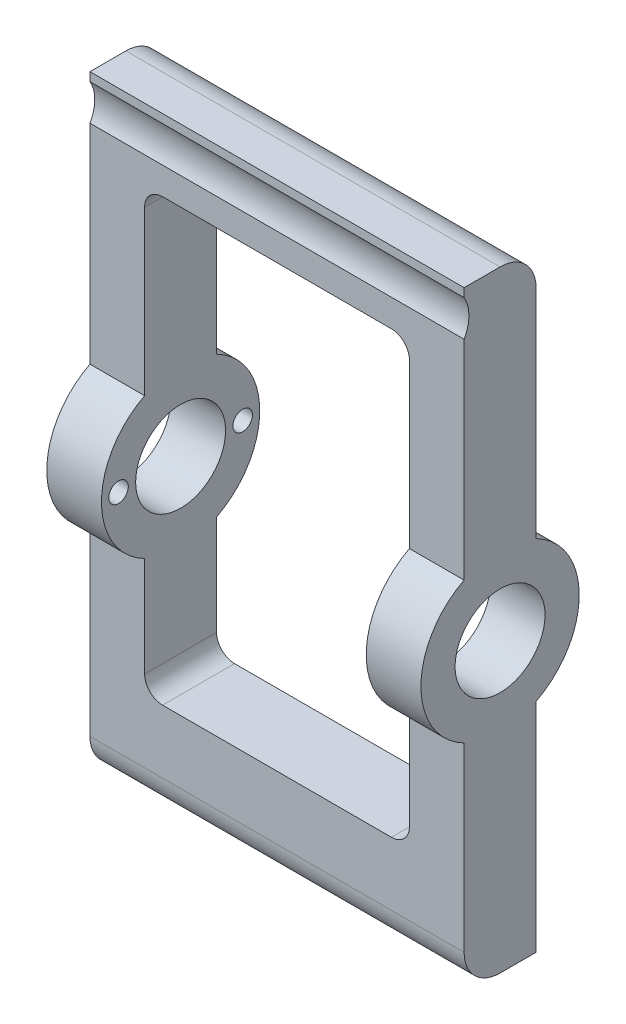
SolidWorks part; units mm, degrees
material "AISI 4130 Steel, annealed at 865C"
ref_plane "Front Plane" through (0, 0, 0) normal (1, 0, 0) x (0, 1, 0)
ref_plane "Top Plane" through (0, 0, 0) normal (0, 0, 1) x (0, 1, 0)
ref_plane "Right Plane" through (0, 0, 0) normal (0, 1, 0) x (-1, 0, 0)
sketch "Sketch1" plane through (0, 0, 0) normal (1, 0, 0) x (0, 1, 0)
  line L0 (12.4434, 6.35) -> (49.276, 6.35)
  line L5 (57.15, 0) -> (-57.15, 0) construction
  line L6 (12.4434, -6.35) -> (57.15, -6.35)
  line L7 (57.15, -6.35) -> (57.15, 6.35)
  line L8 (57.15, 6.35) -> (55.626, 6.35)
  line L9 (12.4434, -6.35) -> (12.4434, 6.35) construction
  line L10 (0, 13.97) -> (0, -13.97) construction
  line L11 (-12.4434, 6.35) -> (-50.8, 6.35)
  line L12 (-12.4434, 6.35) -> (-12.4434, -6.35)
  line L13 (-12.4434, -6.35) -> (-50.8, -6.35)
  line L14 (-50.8, 6.35) -> (-50.8, -6.35)
  line L15 (0, -10.9601) -> (0, 10.9601)
  line L16 (-7.5565, 2.4297) -> (-7.5565, -2.4297)
  line L17 (52.451, 11.8493) -> (49.276, 6.35) construction
  circle A0 centre (0, 0) radius 7.9375
  circle A1 centre (0, 0) radius 13.97
  arc A2 (49.276, 6.35) -> (55.626, 6.35) centre (52.451, 11.8493) ccw
  circle A3 centre (52.451, 11.8493) radius 6.35 construction
  point P9 (0, 0)
  point P17 (12.4434, 0)
  point P28 (0, 0)
  dimension "D1" = 15.875
  dimension "D3" = 27.94
  dimension "D7" = 6.35
  dimension "D2" = 12.7
  dimension "D4" = 57.15
  dimension "D5" = 50.8
  dimension "D6" = 1.524
  dimension "D8" = 6.35
  dimension "D9" = 21.9202
  dimension "D10" = 7.5565
extrude "Boss-Extrude1" add sketch "Sketch1" along normal blind 66.04 contours A1 L11 L14 L13 | L12 A1 | A1 L12 A0 | A2 L0 A1 L6 L7 L8 region at (0, 35.1954, -0.0398) region at (0, 13.2092, 3.1756) region at (0, -32.1337, 0) region at (0, -13.057, 0)
sketch "Sketch2" plane through (0, 0, 0) normal (0, 0, 1) x (0, 1, 0)
  line L0 (0, 0) -> (0, -66.04) construction
  line L1 (-30.099, -9.652) -> (41.275, -9.652)
  line L2 (-33.274, -12.827) -> (-33.274, -53.213)
  line L3 (-30.099, -56.388) -> (41.275, -56.388)
  line L4 (44.45, -12.827) -> (44.45, -53.213)
  line L5 (-12.4434, -66.04) -> (12.4434, -66.04) construction
  line L6 (-12.4434, 0) -> (-50.8, 0) construction
  line L7 (-12.4434, -66.04) -> (-50.8, -66.04) construction
  line L8 (-50.8, -66.04) -> (-50.8, 0) construction
  line L10 (57.15, -66.04) -> (57.15, 0) construction
  arc A0 (44.45, -12.827) -> (41.275, -9.652) centre (41.275, -12.827) ccw
  arc A1 (41.275, -56.388) -> (44.45, -53.213) centre (41.275, -53.213) ccw
  arc A2 (-30.099, -56.388) -> (-33.274, -53.213) centre (-30.099, -53.213) cw
  arc A3 (-33.274, -12.827) -> (-30.099, -9.652) centre (-30.099, -12.827) cw
  dimension "D5" = 3.175
  dimension "D1" = 9.652
  dimension "D2" = 9.652
  dimension "D3" = 17.526
  dimension "D4" = 12.7
extrude "Cut-Extrude1" cut sketch "Sketch2" against normal through all both and the other way through all
fillet "Fillet1" radius 6.35 2 edges at (33.02, -50.8, 6.35) (33.02, 57.15, -6.35)
hole_wizard "Tap Drill for #8-32 Tap1" positions "Sketch3" profile "Sketch4" hole size "#8-32" standard "ANSI Inch" end condition up to next
sketch "Sketch3" plane through (0, 0, 0) normal (-1, 0, 0) x (0, 0, 1)
  point P0 (10.9601, 0)
  point P3 (-10.9601, 0)
sketch "Sketch4" plane through (0, 0, 10.9601) normal (0, 1, 0) x (0, 0, 1)
  line L0 (0, 0) -> (0, 9.652)
  line L1 (0, 9.652) -> (1.7272, 9.652)
  line L2 (1.7272, 9.652) -> (1.7272, 0)
  line L5 (1.7272, 0) -> (0, 0)
  line L11 (0, -6.35) -> (0, 107.95) construction
  dimension "Thru Hole Dia." = 3.4544
  dimension "Thru Hole Depth" = 9.652
equation "\"D10@Sketch1\"=0.5*0.625-0.015"
